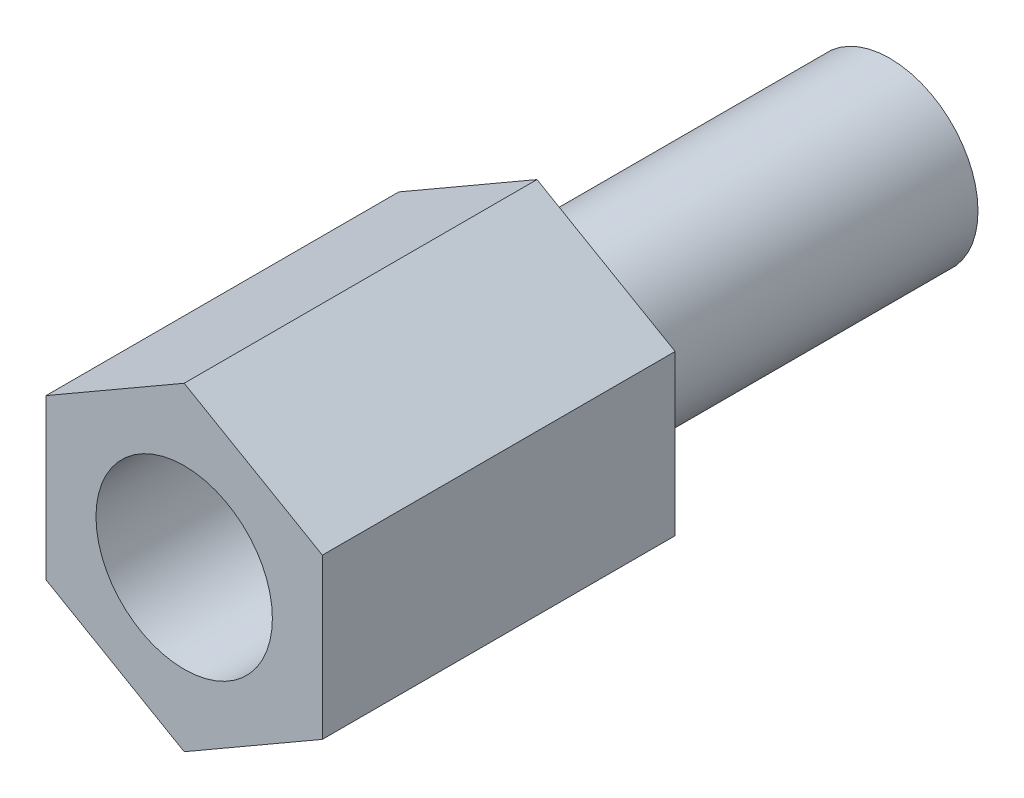
SolidWorks part; units mm, degrees
ref_plane "Front Plane" through (0, 0, 0) normal (1, 0, 0) x (0, 1, 0)
ref_plane "Top Plane" through (0, 0, 0) normal (0, 0, 1) x (0, 1, 0)
ref_plane "Right Plane" through (0, 0, 0) normal (0, 1, 0) x (-1, 0, 0)
sketch "Sketch1" plane through (0, 0, 0) normal (0, 0, 1) x (0, 1, 0)
  line L1 (2.7135, 0) -> (1.3568, 2.35)
  line L2 (1.3568, 2.35) -> (-1.3568, 2.35)
  line L3 (-1.3568, 2.35) -> (-2.7135, 0)
  line L4 (-2.7135, 0) -> (-1.3568, -2.35)
  line L5 (-1.3568, -2.35) -> (1.3568, -2.35)
  line L6 (1.3568, -2.35) -> (2.7135, 0)
  circle A0 centre (0, 0) radius 2.35 construction
  circle A1 centre (0, 0) radius 1.5
  dimension "D1" = 4.7
  dimension "D2" = 3
extrude "Boss-Extrude1" add sketch "Sketch1" along normal blind 6
extrude "Boss-Extrude2" add sketch "Sketch1<2>" against normal blind 6 separate body contours A1 region at (0, 0, 0)
sketch "Sketch1<2>" plane through (0, 0, 0) normal (0, 0, 1) x (0, 1, 0) same geometry as "Sketch1"
